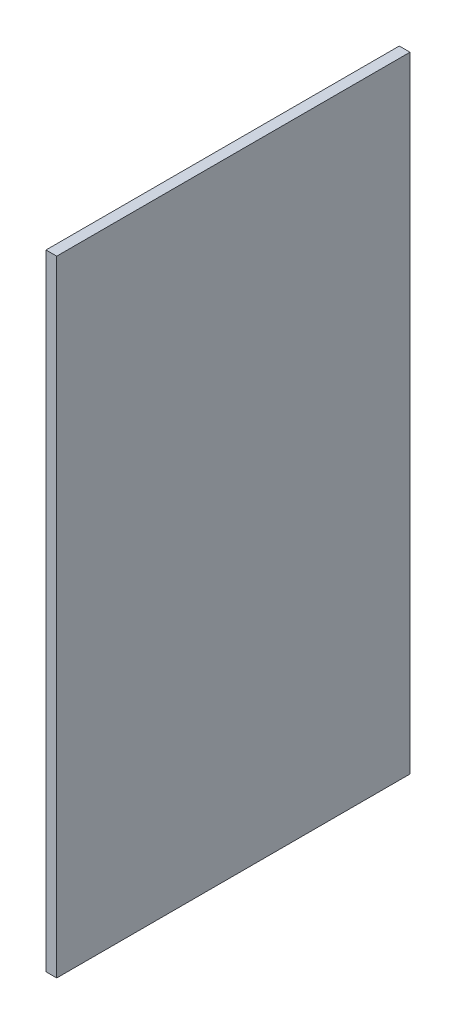
SolidWorks part; units mm, degrees
ref_plane "Front Plane" through (0, 0, 0) normal (1, 0, 0) x (0, 1, 0)
ref_plane "Top Plane" through (0, 0, 0) normal (0, 0, 1) x (0, 1, 0)
ref_plane "Right Plane" through (0, 0, 0) normal (0, 1, 0) x (-1, 0, 0)
sketch "Sketch1" plane through (0, 0, 0) normal (1, 0, 0) x (0, 1, 0)
  line L1 (92.583, -52.3194) -> (-92.583, -52.3194)
  line L2 (92.583, -52.3194) -> (92.583, 52.3194)
  line L3 (92.583, 52.3194) -> (-92.583, 52.3194)
  line L4 (-92.583, -52.3194) -> (-92.583, 52.3194)
  line L5 (92.583, -52.3194) -> (-92.583, 52.3194) construction
  line L6 (92.583, 52.3194) -> (-92.583, -52.3194) construction
  point P0 (0, 0)
extrude "Boss-Extrude1" add sketch "Sketch1" along normal blind 3.175
